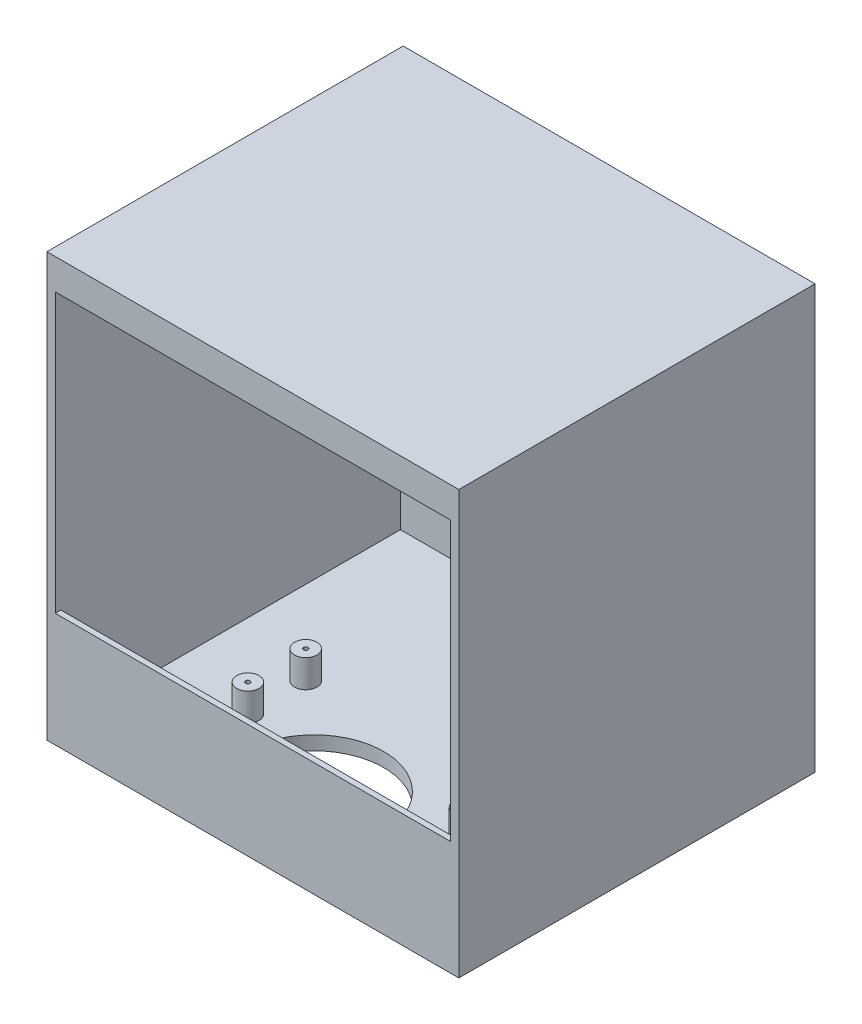
SolidWorks part; units mm, degrees
ref_plane "Front Plane" through (0, 0, 0) normal (0, 0, 1) x (1, 0, 0)
ref_plane "Top Plane" through (0, 0, 0) normal (0, 1, 0) x (1, 0, 0)
ref_plane "Right Plane" through (0, 0, 0) normal (1, 0, 0) x (0, 0, -1)
sketch "Sketch1" plane through (0, 0, 0) normal (0, 0, 1) x (1, 0, 0)
  line L1 (0, 0) -> (469.9, 0)
  line L2 (0, 0) -> (0, -482.6)
  line L3 (0, -482.6) -> (469.9, -482.6)
  line L4 (469.9, 0) -> (469.9, -482.6)
  dimension "D1" = 469.9
  dimension "D2" = 482.6
extrude "full box" add sketch "Sketch1" against normal blind 406.4
sketch "Sketch2" plane through (0, 0, 0) normal (0, 0, 1) x (1, 0, 0)
  line L0 (0, 0) -> (0, -482.6) construction
  line L1 (9.525, -34.925) -> (460.375, -34.925)
  line L2 (9.525, -34.925) -> (9.525, -352.425)
  line L3 (9.525, -352.425) -> (460.375, -352.425)
  line L4 (460.375, -34.925) -> (460.375, -352.425)
  line L5 (0, -482.6) -> (469.9, -482.6) construction
  dimension "D1" = 450.85
  dimension "D2" = 9.525
  dimension "D3" = 317.5
  dimension "D4" = 130.175
extrude "inside cut" cut sketch "Sketch2" against normal blind 393.7
sketch "Sketch3" plane through (0, -352.425, 0) normal (0, 1, 0) x (1, 0, 0)
  line L0 (460.375, 393.7) -> (460.375, 0) construction
  line L1 (9.525, 393.7) -> (460.375, 393.7)
  line L2 (9.525, 393.7) -> (9.525, 6.35)
  line L3 (9.525, 6.35) -> (460.375, 6.35)
  line L4 (460.375, 393.7) -> (460.375, 6.35)
  line L5 (9.525, 0) -> (460.375, 0) construction
  dimension "D1" = 0
  dimension "D2" = 6.35
extrude "floor cut" cut sketch "Sketch3" against normal blind 114.3
sketch "Sketch4" plane through (0, -466.725, 0) normal (0, 1, 0) x (1, 0, 0)
  line L2 (9.525, 6.35) -> (460.375, 6.35) construction
  line L3 (460.375, 6.35) -> (460.375, 393.7) construction
  circle A0 centre (219.075, 85.725) radius 79.375
  dimension "D1" = 158.75
  dimension "D3" = 79.375
  dimension "D2" = 241.3
extrude "drain hole" cut sketch "Sketch4" against normal through all
sketch "Sketch5" plane through (0, -466.725, 0) normal (0, 1, 0) x (1, 0, 0)
  line L0 (460.375, 6.35) -> (460.375, 393.7) construction
  line L1 (460.375, 393.7) -> (9.525, 393.7) construction
  circle A0 centre (104.775, 124.46) radius 12.7
  circle A1 centre (352.425, 124.46) radius 12.7
  circle A2 centre (352.425, 190.5) radius 12.7
  circle A3 centre (104.775, 190.5) radius 12.7
  point P8 (352.425, 361.95)
  point P9 (104.775, 361.95)
  point P15 (104.775, 124.46)
  point P16 (352.425, 124.46)
  point P17 (352.425, 190.5)
  point P19 (104.775, 190.5)
  dimension "D1" = 25.4
  dimension "D5" = 171.45
  dimension "D2" = 107.95
  dimension "D3" = 247.65
  dimension "D4" = 31.75
  dimension "D6" = 66.04
extrude "pegs" add sketch "Sketch5" along normal blind 31.75 separate body
sketch "positions of holes in pegs" plane through (0, -434.975, 0) normal (0, 1, 0) x (1, 0, 0)
  point P0 (104.775, 190.5)
  point P1 (104.775, 124.46)
  point P3 (352.425, 124.46)
  point P5 (352.425, 190.5)
hole_wizard "holes in pegs" positions "Sketch18" profile "Sketch19" tap size "1/4-20" standard "ANSI Inch"
sketch "Sketch18" plane through (0, -434.975, 0) normal (0, 1, 0) x (1, 0, 0)
  point P0 (104.775, 124.46)
  point P3 (104.775, 190.5)
  point P6 (352.425, 190.5)
  point P9 (352.425, 124.46)
sketch "Sketch19" plane through (104.775, -434.975, -124.46) normal (1, 0, 0) x (0, 0, 1)
  line L0 (0, 0) -> (0, 20.5838)
  line L1 (0, 20.5838) -> (2.5527, 19.05)
  line L2 (2.5527, 19.05) -> (2.5527, 0)
  line L5 (2.5527, 0) -> (0, 0)
  line L10 (0, 20.5838) -> (-2.5527, 19.05) construction
  line L11 (0, -6.35) -> (0, 107.95) construction
  dimension "Tap Drill Dia." = 5.1054
  dimension "Tap Drill Depth" = 19.05
  dimension "Drill Angle" = 118
cosmetic thread "Hole Thread9" parameters "D1"=12.7, "D2"=6.35
cosmetic thread "Hole Thread10" parameters "D1"=12.7, "D2"=6.35
cosmetic thread "Hole Thread11" parameters "D1"=12.7, "D2"=6.35
cosmetic thread "Hole Thread12" parameters "D1"=12.7, "D2"=6.35
sketch "holes in floor" plane through (0, -466.725, 0) normal (0, 1, 0) x (1, 0, 0)
  line L0 (460.375, 6.35) -> (460.375, 393.7) construction
  point P0 (104.775, 361.95)
  point P1 (352.425, 361.95)
  dimension "D1" = 171.45
  dimension "D2" = 247.65
  dimension "D3" = 107.95
hole_wizard "1/4-20 Tapped Hole1" positions "Sketch23" profile "Sketch24" tap size "1/4-20" standard "ANSI Inch"
sketch "Sketch23" plane through (0, -466.725, 0) normal (0, 1, 0) x (1, 0, 0)
  point P0 (104.775, 361.95)
  point P3 (352.425, 361.95)
sketch "Sketch24" plane through (104.775, -466.725, -361.95) normal (1, 0, 0) x (0, 0, 1)
  line L0 (0, 0) -> (0, 18.0438)
  line L1 (0, 18.0438) -> (2.5527, 16.51)
  line L2 (2.5527, 16.51) -> (2.5527, 0)
  line L5 (2.5527, 0) -> (0, 0)
  line L10 (0, 18.0438) -> (-2.5527, 16.51) construction
  line L11 (0, -6.35) -> (0, 107.95) construction
  dimension "Tap Drill Dia." = 5.1054
  dimension "Tap Drill Depth" = 16.51
  dimension "Drill Angle" = 118
cosmetic thread "Hole Thread13" parameters "D1"=12.7, "D2"=6.35
cosmetic thread "Hole Thread14" parameters "D1"=12.7, "D2"=6.35
